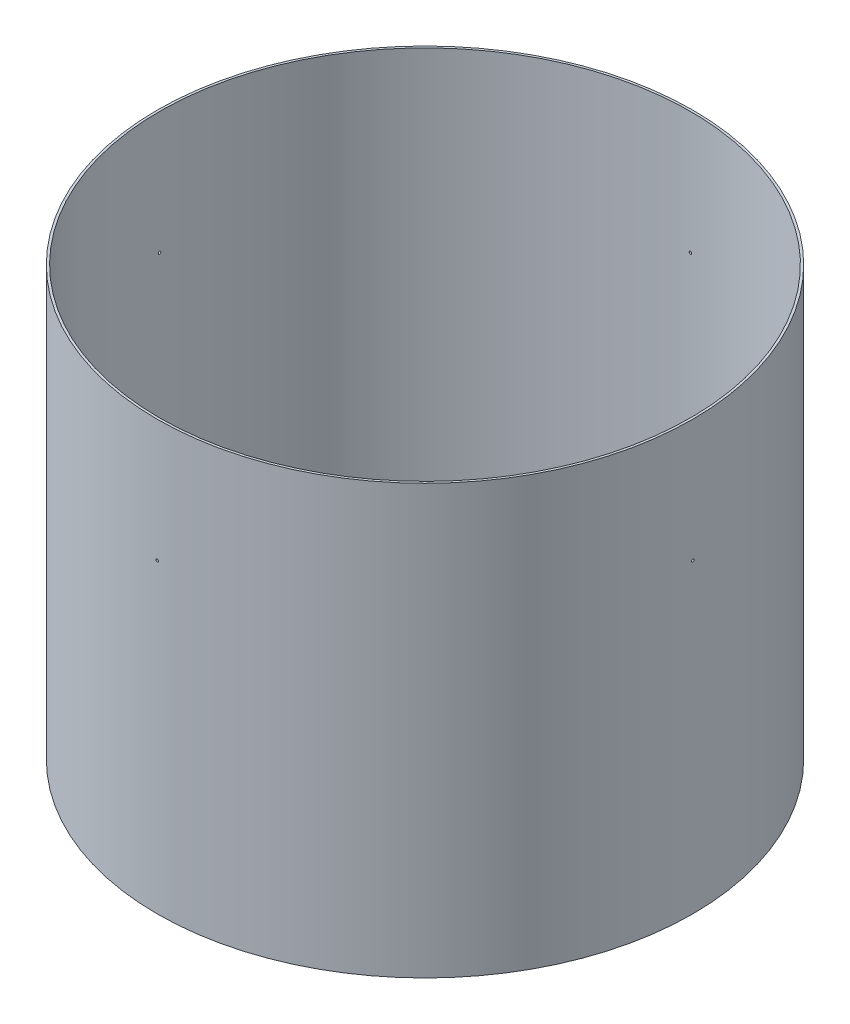
SolidWorks part; units mm, degrees
material "2014 Alloy"
ref_plane "Front Plane" through (0, 0, 0) normal (0, 0, 1) x (1, 0, 0)
ref_plane "Top Plane" through (0, 0, 0) normal (0, 1, 0) x (1, 0, 0)
ref_plane "Right Plane" through (0, 0, 0) normal (1, 0, 0) x (0, 0, -1)
sketch "Sketch9" plane through (0, 0, 0) normal (0, 1, 0) x (1, 0, 0)
  circle A0 centre (0, 0) radius 1750
extrude "Boss-Extrude5" add sketch "Sketch9" along normal blind 2800
sketch "Sketch19" plane through (0, 0, 0) normal (0, 0, 1) x (1, 0, 0)
  circle A0 centre (0, 2000) radius 8.382
  point P2 (0, 0)
extrude "Cut-Extrude11" cut sketch "Sketch19" along normal blind 300 and the other way blind 100 from offset 1800
sketch "Sketch20" plane through (0, 2800, 0) normal (0, 1, 0) x (1, 0, 0)
  circle A0 centre (0, 0) radius 1735
extrude "Cut-Extrude12" cut sketch "Sketch20" against normal blind 2785
pattern_circular "CirPattern1" count 4 every 90 about axis through (0, 2800, 0) along (0, -1, 0) of "Cut-Extrude11"
